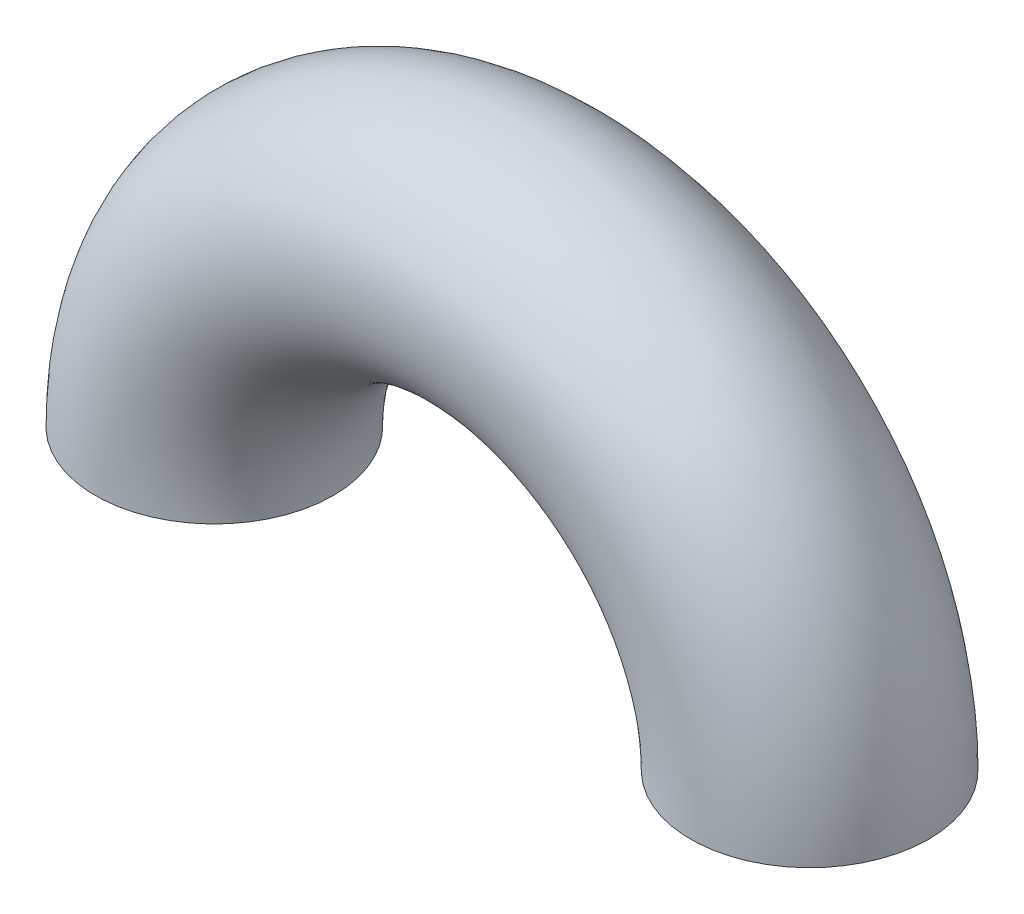
SolidWorks part; units mm, degrees
ref_plane "Front Plane" through (0, 0, 0) normal (0, 0, 1) x (1, 0, 0)
ref_plane "Top Plane" through (0, 0, 0) normal (0, 1, 0) x (1, 0, 0)
ref_plane "Right Plane" through (0, 0, 0) normal (1, 0, 0) x (0, 0, -1)
sketch "Sketch1" plane through (0, 0, 0) normal (0, 0, 1) x (1, 0, 0)
  line L0 (-12.5, 0) -> (37.5, 0) construction
  arc A0 (-12.5, 0) -> (12.5, 0) centre (0, 0) cw
  dimension "D1" = 12.5
sweep "Sweep-Thin1" add path "Sketch1" circular profile diameter 10 parameters "D1"=0.5, "D3"=10
